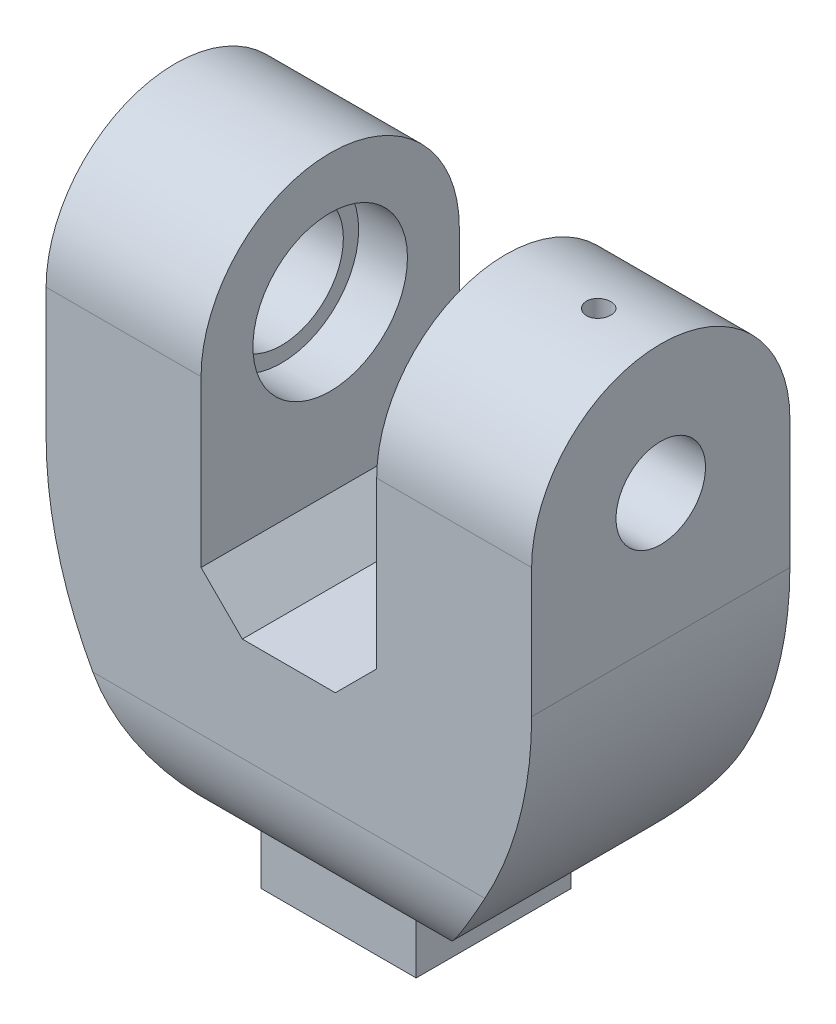
SolidWorks part; units mm, degrees
material "PLA"
ref_plane "Front Plane" through (0, 0, 0) normal (0, 0, 1) x (1, 0, 0)
ref_plane "Top Plane" through (0, 0, 0) normal (0, 1, 0) x (1, 0, 0)
ref_plane "Right Plane" through (0, 0, 0) normal (1, 0, 0) x (0, 0, -1)
sketch "Sketch1" plane through (0, 0, 0) normal (1, 0, 0) x (0, 0, -1)
  circle A0 centre (0, 0) radius 3 construction
  circle A1 centre (0, 0) radius 9.5
  circle A2 centre (0, 0) radius 15.875
  dimension "D1" = 6
  dimension "D2" = 19
  dimension "D3" = 31.75
extrude "Boss-Extrude1" add sketch "Sketch1" along normal blind 6
sketch "Sketch2" plane through (0, 0, 0) normal (-1, 0, 0) x (0, 0, 1)
  circle A0 centre (0, 0) radius 9.5 construction
  circle A1 centre (0, 0) radius 15.875
  circle A2 centre (0, 0) radius 15.875
  circle A3 centre (0, 0) radius 9.5
  circle A4 centre (0, 0) radius 7.62
  circle M3 centre (0, 0) radius 15.875
  circle M4 centre (0, 0) radius 9.5
  dimension "D2" = 15.24
  dimension "D1" = 0
extrude "Boss-Extrude2" add sketch "Sketch2" along normal blind 13.05 contours A4 M4 | M3 M4 region at (0, 0, -15.426) region at (0, 0, -9.2313)
ref_plane "Plane1" through (16.795, 0, 0) normal (1, 0, 0) x (0, 0, -1)
mirror "Mirror2" about plane through (16.795, 0, 0) normal (1, 0, 0) of bodies 102
sketch "Sketch3" plane through (6, 0, 0) normal (1, 0, 0) x (0, 0, -1)
  line L0 (-15.875, 0) -> (-15.875, -38.1)
  line L1 (15.875, 0) -> (15.875, -38.1)
  arc A0 (-15.875, -38.1) -> (15.875, -38.1) centre (0, -38.1) ccw
  circle A1 centre (0, 0) radius 15.875
  circle A2 centre (0, 0) radius 15.875
  circle M2 centre (0, 0) radius 15.875
  dimension "D2" = 38.1
  dimension "D3" = 15.875
  dimension "D1" = 0
extrude "Boss-Extrude3" add sketch "Sketch3" against normal up to surface (19.05 mm away) contours L0 A0 L1 M2 region at (6, -31.5182, 0) up to face at (-13.05, 0, 7.62)
extrude "Boss-Extrude4" add sketch "Sketch3<3>" along normal up to surface (19.05 mm away) from surface contours L0 A0 L1 M2 region at (6, -31.5182, 0) starting at face at (27.59, 0, -15.875)
sketch "Sketch3<3>" plane through (6, 0, 0) normal (1, 0, 0) x (0, 0, -1) same geometry as "Sketch3"
sketch "Sketch4" plane through (6, 0, 0) normal (1, 0, 0) x (0, 0, -1)
  line L0 (-15.875, -25.4) -> (15.875, -25.4)
  line L2 (-15.875, 0) -> (-15.875, -38.1)
  line L3 (15.875, -38.1) -> (15.875, 0)
  line L4 (-15.875, 0) -> (-15.875, -38.1)
  line L5 (15.875, -38.1) -> (15.875, 0)
  arc A2 (15.875, 0) -> (-15.875, 0) centre (0, 0) ccw
  arc A3 (-15.875, -38.1) -> (15.875, -38.1) centre (0, -38.1) ccw
  arc A4 (15.875, 0) -> (-15.875, 0) centre (0, 0) ccw
  arc A5 (-15.875, -38.1) -> (15.875, -38.1) centre (0, -38.1) ccw
  line M7 (-15.875, 0) -> (-15.875, -38.1)
  arc M8 (-15.875, -38.1) -> (15.875, -38.1) centre (0, -38.1) ccw
  line M9 (15.875, -38.1) -> (15.875, 0)
  dimension "D2" = 25.4
  dimension "D1" = 0
extrude "Boss-Extrude5" add sketch "Sketch4" along normal up to surface (21.59 mm away) contours L0 M7 M8 M9 region at (6, -38.2335, 0)
sketch "Sketch5" plane through (0, 0, 15.875) normal (0, 0, 1) x (1, 0, 0)
  line L0 (6, -15.875) -> (-13.05, -15.875) construction
  line L2 (-13.05, -38.1) -> (-13.05, -53.975) construction
  line L8 (6, 0) -> (-13.05, 0)
  line L9 (-13.05, 0) -> (-13.05, -38.1)
  line L10 (-13.05, -38.1) -> (46.64, -38.1)
  line L11 (46.64, -38.1) -> (46.64, 0)
  line L12 (46.64, 0) -> (27.59, 0)
  line L13 (27.59, 0) -> (27.59, -25.4)
  line L14 (27.59, -25.4) -> (6, -25.4)
  line L15 (6, -25.4) -> (6, 0)
  line L16 (6, 0) -> (-13.05, 0)
  line L17 (-13.05, 0) -> (-13.05, -38.1)
  line L18 (-13.05, -38.1) -> (46.64, -38.1)
  line L19 (46.64, -38.1) -> (46.64, 0)
  line L20 (46.64, 0) -> (27.59, 0)
  line L21 (27.59, 0) -> (27.59, -25.4)
  line L22 (27.59, -25.4) -> (6, -25.4)
  line L23 (6, -25.4) -> (6, 0)
  line L25 (-13.05, -38.1) -> (-13.05, -53.975)
  line L26 (-13.05, -53.975) -> (46.64, -53.975)
  line L27 (46.64, -53.975) -> (46.64, -38.1)
  line L28 (-13.05, -15.875) -> (7.27, -53.975)
  line L29 (46.64, -15.875) -> (26.32, -53.975)
  line L30 (-13.05, -53.975) -> (46.64, -53.975) construction
  line L31 (16.795, -17.4625) -> (16.795, 17.4625) construction
  arc A0 (-13.05, -15.875) -> (7.27, -53.975) centre (32.8287, -15.875) ccw
  arc A1 (46.64, -15.875) -> (26.32, -53.975) centre (0.7613, -15.875) cw
  line M14 (-13.05, -38.1) -> (46.64, -38.1)
  line M15 (46.64, -38.1) -> (46.64, 0)
  dimension "D2" = 15.875
  dimension "D3" = 19.05
  dimension "D1" = 0
extrude "Cut-Extrude1" cut sketch "Sketch5" against normal through all contours L28 L25 L26 M14 | L28 L17 M14 | L29 L26 L27 M14 | L29 M15 M14 region at (-11.3474, -32.6157, 15.875) region at (-6.3907, -47.6285, 15.875) region at (44.9374, -32.6157, 15.875) region at (39.9807, -47.6285, 15.875)
sketch "Sketch9" plane through (0, -25.4, 0) normal (0, 1, 0) x (1, 0, 0)
  line L0 (5.7854, 0) -> (27.3575, 0) construction
  line L1 (16.795, 15.875) -> (16.795, -15.875) construction
  line L2 (27.59, 15.875) -> (6, 15.875) construction
  line L4 (27.59, -15.875) -> (27.59, 15.875)
  line L5 (27.59, 15.875) -> (6, 15.875)
  line L6 (6, 15.875) -> (6, -15.875)
  line L7 (6, -15.875) -> (27.59, -15.875)
  line L8 (27.59, -15.875) -> (27.59, 15.875)
  line L9 (27.59, 15.875) -> (6, 15.875)
  line L10 (6, 15.875) -> (6, -15.875)
  line L11 (6, -15.875) -> (27.59, -15.875)
  line L12 (7.0465, -9.525) -> (26.0965, -9.525)
  line L13 (7.0465, -9.525) -> (7.0465, 9.525)
  line L14 (7.0465, 9.525) -> (26.0965, 9.525)
  line L15 (26.0965, -9.525) -> (26.0965, 9.525)
  line L16 (7.0465, -9.525) -> (26.0965, 9.525) construction
  line L17 (7.0465, 9.525) -> (26.0965, -9.525) construction
  point P12 (16.5715, 0)
  dimension "D2" = 19.05
  dimension "D1" = 0
extrude "Boss-Extrude8" add sketch "Sketch9" against normal blind 31.75 contours L12 L15 L14 L13 region at (16.5715, -25.4, 0)
chamfer "Chamfer1" distance 5.08 angle 45 2 edges at (27.59, -25.4, 0) (6, -25.4, 0)
sketch "Sketch6" plane through (46.64, 0, 0) normal (1, 0, 0) x (0, 0, -1)
  line L3 (-15.875, 0) -> (-15.875, -15.875)
  line L4 (-15.875, -15.875) -> (15.875, -15.875)
  line L5 (15.875, -15.875) -> (15.875, 0)
  line L6 (-15.875, 0) -> (-15.875, -15.875)
  line L8 (15.875, -15.875) -> (15.875, 0)
  line L9 (-15.875, -15.875) -> (15.875, -15.875)
  circle A0 centre (0, 0) radius 7.62 construction
  arc A1 (15.875, 0) -> (-15.875, 0) centre (0, 0) ccw
  arc A2 (15.875, 0) -> (-15.875, 0) centre (0, 0) ccw
  circle A3 centre (0, 0) radius 7.62
  circle A4 centre (0, 0) radius 5.25
  circle M14 centre (0, 0) radius 7.62
  dimension "D2" = 10.5
  dimension "D1" = 0
extrude "Boss-Extrude6" add sketch "Sketch6" against normal up to surface (13.05 mm away) contours A4 M14 region at (46.64, 0, 7.4045) up to face at (33.59, 0, 7.62)
sketch "Sketch7" plane through (-13.05, 0, 0) normal (-1, 0, 0) x (0, 0, 1)
  line L0 (0, 0) -> (0, 12.7) construction
  line L3 (-15.875, 0) -> (-15.875, -15.875)
  line L4 (-15.875, -15.875) -> (15.875, -15.875)
  line L5 (15.875, -15.875) -> (15.875, 0)
  line L6 (-15.875, 0) -> (-15.875, -15.875)
  line L8 (15.875, -15.875) -> (15.875, 0)
  line L10 (-15.875, -15.875) -> (15.875, -15.875)
  circle A0 centre (0, 0) radius 7.62 construction
  arc A1 (15.875, 0) -> (-15.875, 0) centre (0, 0) ccw
  arc A2 (15.875, 0) -> (-15.875, 0) centre (0, 0) ccw
  circle A3 centre (0, 0) radius 7.62
  circle A4 centre (0, 12.7) radius 1.5
  circle A5 centre (0, -12.7) radius 1.5
  dimension "D2" = 3
  dimension "D5" = 3
  dimension "D3" = 12.7
  dimension "D4" = 12.7
  dimension "D1" = 0
extrude "Cut-Extrude2" cut sketch "Sketch7" against normal blind 12.7 contours A4 | A5 region at (-13.05, 12.7, 0) region at (-13.05, -12.7, 0)
ref_plane "Plane2" through (0, 15.875, 0) normal (0, 1, 0) x (1, 0, 0)
sketch "Sketch8" plane through (0, 15.875, 0) normal (0, 1, 0) x (1, 0, 0)
  line L0 (46.64, -15.875) -> (46.64, 15.875) construction
  circle A0 centre (39.02, 0) radius 1.5
  dimension "D1" = 3
  dimension "D2" = 7.62
extrude "Cut-Extrude3" cut sketch "Sketch8" against normal up to surface (10.8438 mm away) up to face at (33.59, 0, -5.25)
sketch "Sketch10" plane through (46.64, 0, 0) normal (1, 0, 0) x (0, 0, -1)
  circle A0 centre (0, 0) radius 5.5
  circle M5 centre (0, 0) radius 5.25
  dimension "D1" = 11
extrude "Cut-Extrude4" cut sketch "Sketch10" against normal up to surface (13.05 mm away) contours M5 | A0 M5 region at (46.64, 0, 5.3444) region at (46.64, 0, 0) up to face at (33.59, 0, -9.5)
